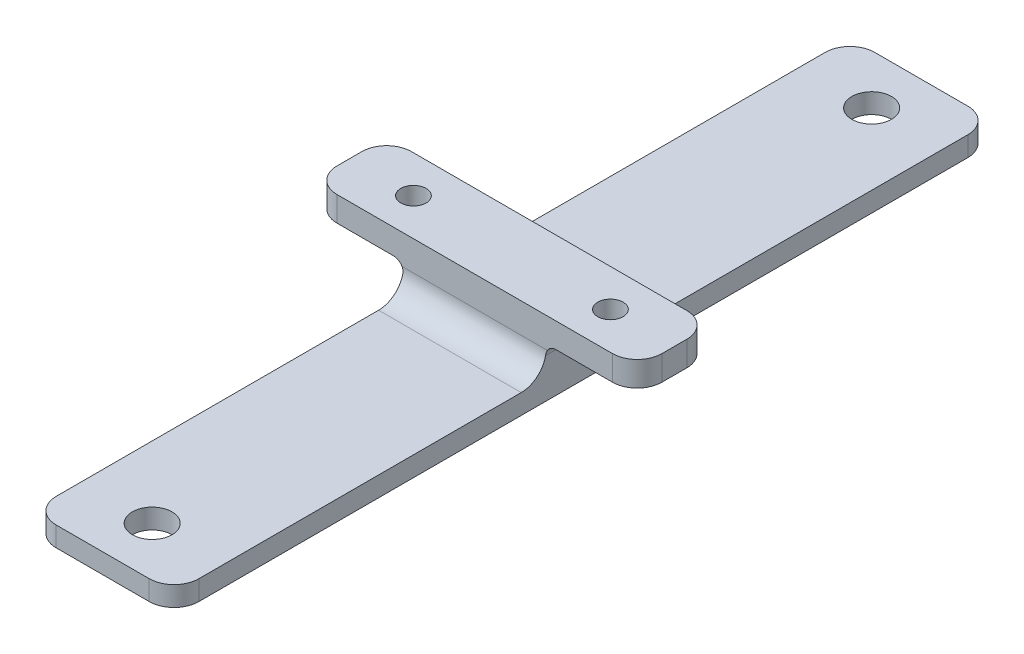
SolidWorks part; units mm, degrees
ref_plane "Front Plane" through (0, 0, 0) normal (0, 0, 1) x (1, 0, 0)
ref_plane "Top Plane" through (0, 0, 0) normal (0, 1, 0) x (1, 0, 0)
ref_plane "Right Plane" through (0, 0, 0) normal (1, 0, 0) x (0, 0, -1)
sketch "Sketch1" plane through (0, 1402.6616, 0) normal (0, 1, 0) x (1, 0, 0)
  line L1 (912.3713, -281.0619) -> (883.6213, -281.0619)
  line L2 (912.3713, -281.0619) -> (912.3713, -116.0935)
  line L3 (912.3713, -116.0935) -> (883.6213, -116.0935)
  line L4 (883.6213, -281.0619) -> (883.6213, -116.0935)
  line L6 (907.3713, -116.0935) -> (888.6213, -116.0935) construction
  circle A0 centre (897.9963, -126.0935) radius 4
  circle A1 centre (897.9963, -271.0935) radius 4
ref_plane "Plane1" through (883.6213, 1402.6616, 121.0935) normal (0, 0, 1) x (1, 0, 0)
extrude "Boss-Extrude1" add sketch "Sketch1" along normal blind 4
sketch "Sketch3" plane through (0, 1406.6616, 0) normal (0, 1, 0) x (1, 0, 0)
  line L0 (912.3713, -281.0619) -> (912.3713, -116.0935) construction
  line L1 (883.6213, -191.0935) -> (912.3713, -191.0935)
  line L2 (883.6213, -191.0935) -> (883.6213, -206.0935)
  line L3 (883.6213, -206.0935) -> (912.3713, -206.0935)
  line L4 (912.3713, -191.0935) -> (912.3713, -206.0935)
  line L5 (883.6213, -191.0935) -> (912.3713, -206.0935) construction
  line L6 (883.6213, -206.0935) -> (912.3713, -191.0935) construction
  point P0 (897.9963, -198.5935)
extrude "Boss-Extrude2" add sketch "Sketch3" along normal blind 6
sketch "Sketch4" plane through (0, 1412.6616, 0) normal (0, 1, 0) x (1, 0, 0)
  line L0 (930.7463, -228.3435) -> (930.7463, -168.8435) construction
  line L1 (865.2463, -191.0935) -> (930.7463, -191.0935)
  line L2 (865.2463, -191.0935) -> (865.2463, -206.0935)
  line L3 (865.2463, -206.0935) -> (930.7463, -206.0935)
  line L4 (930.7463, -191.0935) -> (930.7463, -206.0935)
  line L5 (865.2463, -191.0935) -> (930.7463, -206.0935) construction
  line L6 (865.2463, -206.0935) -> (930.7463, -191.0935) construction
  circle A0 centre (917.8463, -198.5935) radius 2.55
  circle A1 centre (878.1463, -198.5935) radius 2.55
  point P0 (897.9963, -198.5935)
  dimension "D1" = 5.1
extrude "Boss-Extrude3" add sketch "Sketch4" along normal up to surface (5 mm away)
fillet "Fillet1" radius 5 10 edges at (912.3713, 1404.6616, 281.0619) (883.6213, 1404.6616, 281.0619) (930.7463, 1415.1616, 191.0935) (930.7463, 1415.1616, 206.0935) (865.2463, 1415.1616, 206.0935) (865.2463, 1415.1616, 191.0935) (912.3713, 1404.6616, 116.0935) (883.6213, 1404.6616, 116.0935) (897.9963, 1406.6616, 206.0935) (897.9963, 1406.6616, 191.0935)
fillet "Fillet2" radius 2 2 edges at (883.6213, 1412.6616, 198.5935) (912.3713, 1412.6616, 198.5935)
